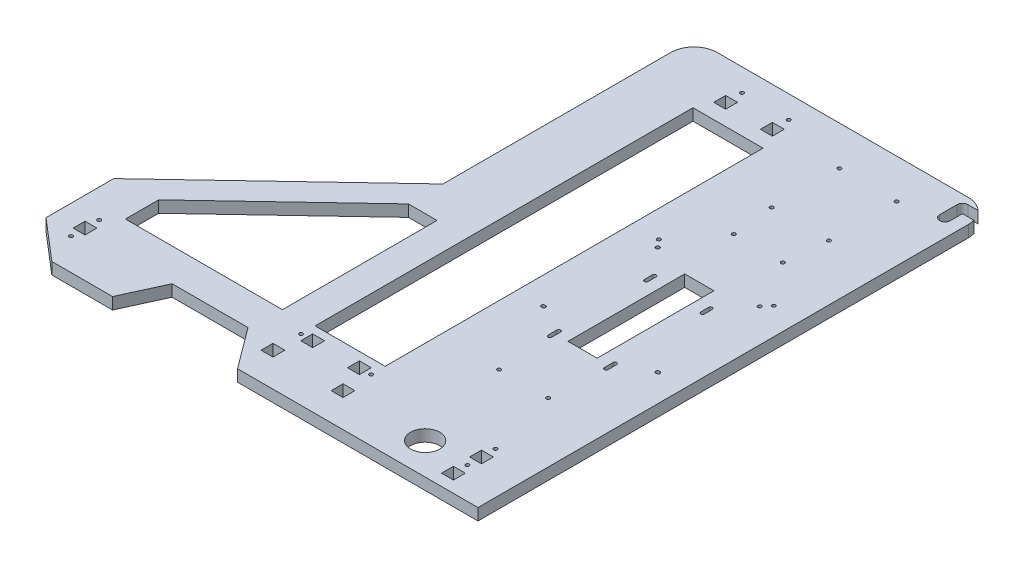
SolidWorks part; units mm, degrees
ref_plane "Front Plane" through (0, 0, 0) normal (0, 0, 1) x (1, 0, 0)
ref_plane "Top Plane" through (0, 0, 0) normal (0, 1, 0) x (1, 0, 0)
ref_plane "Right Plane" through (0, 0, 0) normal (1, 0, 0) x (0, 0, -1)
sketch "Sketch1" plane through (0, 0, 0) normal (0, 1, 0) x (1, 0, 0)
  line L0 (0, 0) -> (-235, 0)
  line L1 (-235, 0) -> (-235, -215)
  line L2 (-235, -215) -> (-380, -352)
  line L3 (-380, -352) -> (-380, -410)
  line L4 (-380, -410) -> (-345, -440)
  line L5 (-345, -440) -> (-293, -440)
  line L6 (-293, -440) -> (-277, -405)
  line L7 (-277, -405) -> (-212, -405)
  line L8 (-212, -405) -> (-185.9255, -440)
  line L9 (-185.9255, -440) -> (0, -440)
  line L10 (0, 0) -> (0, -440)
  line L12 (-293, -440) -> (-185.9255, -440) construction
  dimension "D3" = 235
  dimension "D5" = 58
  dimension "D13" = 190
  dimension "D7" = 35
  dimension "D2" = 126.686
  dimension "D11" = 65
  dimension "D15" = 52
  dimension "D12" = 30
  dimension "D10" = 35
  dimension "D14" = 16
  dimension "D6" = 380
  dimension "D4" = 440
extrude "Boss-Extrude1" add sketch "Sketch1" along normal blind 10
sketch "Sketch16" plane through (0, 10, 0) normal (0, 1, 0) x (1, 0, 0)
  line L0 (0, -440) -> (20, -440)
  line L1 (20, -440) -> (20, 0)
  line L2 (20, 0) -> (0, 0)
  line L3 (0, 0) -> (0, -440)
  dimension "D1" = 20
  dimension "D2" = 90
extrude "Boss-Extrude2" add sketch "Sketch16" against normal through all
sketch "Sketch2" plane through (0, 10, 0) normal (0, 1, 0) x (1, 0, 0)
  line L0 (-235, -215) -> (-235, -405) construction
  line L1 (-277, -405) -> (-212, -405) construction
  line L2 (-345, -440) -> (-345, -318.931) construction
  line L3 (-235, -215) -> (-380, -352) construction
  line L4 (-345, -348.5097) -> (-235, -244.5787)
  line L5 (-235, -244.5787) -> (-210.5, -244.5787)
  line L6 (-210.5, -244.5787) -> (-210.5, -377)
  line L7 (-210.5, -377) -> (-345, -377)
  line L8 (-345, -377) -> (-345, -348.5097)
  line L9 (0, -440) -> (0, 0) construction
  line L10 (-184.5, -375) -> (-124.5, -375)
  line L11 (-184.5, -375) -> (-184.5, -51.35)
  line L12 (-184.5, -51.35) -> (-124.5, -51.35)
  line L13 (-124.5, -375) -> (-124.5, -51.35)
  line L14 (-124.5, -387.1) -> (-184.5, -387.1) construction
  line L15 (-16, -440) -> (-16, 0) construction
  line L16 (20, 0) -> (-235, 0) construction
  line L17 (-355.55, -430.9571) -> (-355.55, -328.899) construction
  line L18 (-21.1, -430.1) -> (-10.9, -430.1)
  line L19 (-21.1, -430.1) -> (-21.1, -419.9)
  line L20 (-21.1, -419.9) -> (-10.9, -419.9)
  line L21 (-10.9, -430.1) -> (-10.9, -419.9)
  line L22 (-21.1, -430.1) -> (-10.9, -419.9) construction
  line L23 (-21.1, -419.9) -> (-10.9, -430.1) construction
  line L24 (-21.1, -406.1) -> (-10.9, -406.1)
  line L25 (-21.1, -406.1) -> (-21.1, -395.9)
  line L26 (-21.1, -395.9) -> (-10.9, -395.9)
  line L27 (-10.9, -406.1) -> (-10.9, -395.9)
  line L28 (-21.1, -406.1) -> (-10.9, -395.9) construction
  line L29 (-21.1, -395.9) -> (-10.9, -406.1) construction
  line L30 (-380, -410) -> (-345, -440) construction
  line L32 (-350.45, -395.9) -> (-360.65, -395.9)
  line L33 (-350.45, -395.9) -> (-350.45, -406.1)
  line L34 (-350.45, -406.1) -> (-360.65, -406.1)
  line L35 (-360.65, -395.9) -> (-360.65, -406.1)
  line L36 (-350.45, -395.9) -> (-360.65, -406.1) construction
  line L37 (-350.45, -406.1) -> (-360.65, -395.9) construction
  line L38 (-185.9255, -440) -> (20, -440) construction
  line L39 (-185.9255, -440) -> (20, -440) construction
  line L40 (-173.924, -33.35) -> (-113.924, -33.35) construction
  line L41 (-154.5, -51.35) -> (-154.5, -33.35) construction
  line L42 (-179.6, -28.25) -> (-169.4, -28.25)
  line L43 (-179.6, -28.25) -> (-179.6, -38.45)
  line L44 (-179.6, -38.45) -> (-169.4, -38.45)
  line L45 (-169.4, -28.25) -> (-169.4, -38.45)
  line L46 (-179.6, -28.25) -> (-169.4, -38.45) construction
  line L47 (-179.6, -38.45) -> (-169.4, -28.25) construction
  line L48 (-129.4, -38.45) -> (-139.6, -28.25) construction
  line L49 (-129.4, -28.25) -> (-139.6, -38.45) construction
  line L50 (-139.6, -28.25) -> (-139.6, -38.45)
  line L51 (-129.4, -38.45) -> (-139.6, -38.45)
  line L52 (-129.4, -28.25) -> (-129.4, -38.45)
  line L53 (-129.4, -28.25) -> (-139.6, -28.25)
  line L54 (-174.5, -33.35) -> (-174.5, -19.35) construction
  line L55 (-134.5, -33.35) -> (-134.5, -19.35) construction
  line L56 (-154.5, -375) -> (-154.5, -440) construction
  line L57 (-174.5, -387.1) -> (-134.5, -387.1) construction
  line L58 (-129.4, -392.2) -> (-139.6, -382) construction
  line L59 (-179.6, -382) -> (-169.4, -382)
  line L60 (-179.6, -382) -> (-179.6, -392.2)
  line L61 (-179.6, -392.2) -> (-169.4, -392.2)
  line L62 (-169.4, -382) -> (-169.4, -392.2)
  line L63 (-179.6, -382) -> (-169.4, -392.2) construction
  line L64 (-179.6, -392.2) -> (-169.4, -382) construction
  line L65 (-129.4, -382) -> (-139.6, -392.2) construction
  line L66 (-139.6, -382) -> (-139.6, -392.2)
  line L67 (-129.4, -392.2) -> (-139.6, -392.2)
  line L68 (-129.4, -382) -> (-129.4, -392.2)
  line L69 (-129.4, -382) -> (-139.6, -382)
  line L70 (-119.4, -416.2) -> (-129.6, -406) construction
  line L71 (-189.6, -406) -> (-179.4, -406)
  line L72 (-189.6, -406) -> (-189.6, -416.2)
  line L73 (-189.6, -416.2) -> (-179.4, -416.2)
  line L74 (-179.4, -406) -> (-179.4, -416.2)
  line L75 (-189.6, -406) -> (-179.4, -416.2) construction
  line L76 (-189.6, -416.2) -> (-179.4, -406) construction
  line L77 (-119.4, -406) -> (-129.6, -416.2) construction
  line L78 (-129.6, -406) -> (-129.6, -416.2)
  line L79 (-119.4, -416.2) -> (-129.6, -416.2)
  line L80 (-119.4, -406) -> (-119.4, -416.2)
  line L81 (-119.4, -406) -> (-129.6, -406)
  line L82 (-360.65, -395.9) -> (-10.9, -395.9) construction
  circle A0 centre (-16, -413) radius 1.55
  circle A1 centre (-16, -389) radius 1.55
  circle A2 centre (-355.55, -413) radius 1.55
  circle A3 centre (-355.55, -389) radius 1.55
  circle A4 centre (-174.5, -19.35) radius 1.55
  circle A5 centre (-134.5, -19.35) radius 1.55
  circle A6 centre (-124.5, -387.1) radius 1.55
  circle A7 centre (-184.5, -387.1) radius 1.55
  point P25 (-16, -425)
  point P30 (-16, -401)
  point P44 (-355.55, -401)
  point P61 (-174.5, -33.35)
  point P72 (-134.5, -33.35)
  point P85 (-174.5, -387.1)
  point P94 (-134.5, -387.1)
  point P95 (-184.5, -411.1)
  point P104 (-124.5, -411.1)
  point P105 (-154.5, -387.1)
  dimension "D13" = 3.1
  dimension "D14" = 3.1
  dimension "D23" = 3.1
  dimension "D24" = 3.1
  dimension "D31" = 3.1
  dimension "D37" = 3.1
  dimension "D1" = 21.5
  dimension "D2" = 28
  dimension "D3" = 24.5
  dimension "D4" = 60
  dimension "D7" = 26
  dimension "D8" = 10.2
  dimension "D9" = 10.2
  dimension "D10" = 10.2
  dimension "D11" = 10.2
  dimension "D12" = 24
  dimension "D15" = 24
  dimension "D19" = 10.2
  dimension "D20" = 10.2
  dimension "D26" = 12
  dimension "D27" = 10.2
  dimension "D28" = 10.2
  dimension "D33" = 10.2
  dimension "D38" = 10.2
  dimension "D39" = 10.2
  dimension "D41" = 24
  dimension "D34" = 30
  dimension "D36" = 12.1
  dimension "D30" = 18
  dimension "D29" = 40
  dimension "D17" = 15
  dimension "D32" = 14
  dimension "D35" = 20
  dimension "D16" = 12
  dimension "D21" = 90
  dimension "D25" = 24
  dimension "D5" = 353.75
  dimension "D22" = 349.75
  dimension "D40" = 30
  dimension "D6" = 65
  dimension "D42" = 0
  dimension "D43" = 0
  dimension "D18" = 16
extrude "Cut-Extrude1" cut sketch "Sketch2" against normal through all
fillet "Fillet1" radius 20 2 edges at (-235, 5, 0) (20, 5, 0)
sketch "Sketch11" plane through (0, 10, 0) normal (0, 1, 0) x (1, 0, 0)
  line L0 (-124.5, -213.175) -> (20, -213.175) construction
  line L1 (20, -440) -> (20, -20) construction
  line L3 (-52.25, -213.175) -> (-52.25, -440) construction
  line L6 (-124.5, -375) -> (-124.5, -51.35) construction
  line L8 (-185.9255, -440) -> (20, -440) construction
  circle A0 centre (-52.25, -413) radius 12.5
  circle A1 centre (-16, -413) radius 1.55 construction
  dimension "D1" = 25
  dimension "D2" = 0
  dimension "D3" = 0
extrude "WiringHole" cut sketch "Sketch11" against normal through all
sketch "Sketch9" [suppressed] plane through (0, 10, 0) normal (0, 1, 0) x (1, 0, 0)
  line L0 (-52.25, -400.5) -> (-52.25, 0) construction
  line L1 (0, 0) -> (-215, 0) construction
  line L2 (-124.5, -213.175) -> (20, -213.175) construction
  line L3 (-124.5, -375) -> (-124.5, -51.35) construction
  line L4 (-4.75, -124.675) -> (-4.75, -301.675) construction
  line L6 (-99.75, -124.675) -> (-4.75, -124.675) construction
  line L7 (-4.75, -301.675) -> (-99.75, -301.675) construction
  line L8 (-99.75, -301.675) -> (-99.75, -124.675) construction
  line L9 (20, -440) -> (20, -20) construction
  circle A0 centre (-52.25, -413) radius 12.5 construction
  circle A1 centre (-99.75, -124.675) radius 1.55
  circle A2 centre (-4.75, -124.675) radius 1.55
  circle A3 centre (-4.75, -301.675) radius 1.55
  circle A4 centre (-99.75, -301.675) radius 1.55
  dimension "D3" = 3.1
  dimension "D4" = 3.1
  dimension "D1" = 95
  dimension "D2" = 177
  dimension "D5" = 47.5
extrude "MountingHoles-PSU" [suppressed] cut sketch "Sketch9" against normal through all
sketch "Sketch10" plane through (0, 10, 0) normal (0, 1, 0) x (1, 0, 0)
  line L0 (-124.5, -213.175) -> (20, -213.175) construction
  line L1 (20, -440) -> (20, -20) construction
  line L2 (-64.75, -228.175) -> (-39.75, -228.175) construction
  line L3 (-52.25, -213.175) -> (-52.25, 0) construction
  line L7 (-124.5, -375) -> (-124.5, -51.35) construction
  line L8 (-64.75, -278.175) -> (-39.75, -278.175)
  line L9 (-64.75, -278.175) -> (-64.75, -178.175)
  line L10 (-64.75, -178.175) -> (-39.75, -178.175)
  line L11 (-39.75, -278.175) -> (-39.75, -178.175)
  line L12 (-64.75, -278.175) -> (-39.75, -178.175) construction
  line L13 (-64.75, -178.175) -> (-39.75, -278.175) construction
  line L15 (0, 0) -> (-215, 0) construction
  line L17 (-52.25, -213.175) -> (-52.25, -440) construction
  line L18 (-185.9255, -440) -> (20, -440) construction
  line L19 (-64.75, -213.175) -> (-39.75, -213.175) construction
  line L20 (-52.25, -278.175) -> (-52.25, -178.175) construction
  dimension "D1" = 25
  dimension "D2" = 100
  dimension "D3" = 0
  dimension "D4" = 0
  dimension "D5" = 0
  dimension "D6" = 15
extrude "WiringSlot" cut sketch "Sketch10" against normal through all
sketch "CenterLines" plane through (0, 10, 0) normal (0, 1, 0) x (1, 0, 0)
  line L0 (-52.25, -278.175) -> (-52.25, -178.175) construction
  line L1 (-64.75, -278.175) -> (-39.75, -278.175) construction
  line L2 (-39.75, -178.175) -> (-64.75, -178.175) construction
  line L3 (-64.75, -228.175) -> (-39.75, -228.175) construction
  line L4 (-64.75, -178.175) -> (-64.75, -278.175) construction
  line L5 (-39.75, -278.175) -> (-39.75, -178.175) construction
ref_plane "Plane1" through (-52.25, 0, 0) normal (1, 0, 0) x (0, 0, -1)
sketch "Sketch6" plane through (0, 10, 0) normal (0, 1, 0) x (1, 0, 0)
  line L0 (-52.25, -278.175) -> (-52.25, -178.175) construction
  line L1 (-76.35, -237.025) -> (-28.15, -237.025) construction
  line L2 (-28.15, -192.575) -> (-28.15, -275.075) construction
  line L3 (-64.75, -278.175) -> (-39.75, -278.175) construction
  line L4 (-64.75, -245.875) -> (-39.75, -245.875) construction
  line L5 (-39.75, -178.175) -> (-64.75, -178.175) construction
  line L6 (-28.15, -192.575) -> (-28.15, -199.575) construction
  line L7 (-26.6, -192.575) -> (-26.6, -199.575)
  line L8 (-29.7, -192.575) -> (-29.7, -199.575)
  line L9 (-64.75, -228.175) -> (-39.75, -228.175) construction
  line L10 (-64.75, -178.175) -> (-64.75, -278.175) construction
  line L11 (-39.75, -278.175) -> (-39.75, -178.175) construction
  line L12 (-28.15, -282.075) -> (-28.15, -275.075) construction
  line L13 (-29.7, -282.075) -> (-29.7, -275.075)
  line L14 (-76.35, -274.475) -> (-76.35, -199.575) construction
  line L15 (-28.15, -282.075) -> (-28.15, -199.575) construction
  line L16 (-26.6, -282.075) -> (-26.6, -275.075)
  arc A2 (-26.6, -192.575) -> (-29.7, -192.575) centre (-28.15, -192.575) ccw
  arc A3 (-29.7, -199.575) -> (-26.6, -199.575) centre (-28.15, -199.575) ccw
  circle A4 centre (-76.35, -274.475) radius 1.55
  circle A6 centre (-76.35, -199.575) radius 1.55
  arc A8 (-29.7, -282.075) -> (-26.6, -282.075) centre (-28.15, -282.075) ccw
  arc A9 (-26.6, -275.075) -> (-29.7, -275.075) centre (-28.15, -275.075) ccw
  point P20 (-28.15, -196.075)
  point P25 (-28.15, -278.575)
  dimension "D8" = 3.1
  dimension "D12" = 3.1
  dimension "D4" = 1.55
  dimension "D5" = 1.55
  dimension "D11" = 82.5
  dimension "D14" = 74.9
  dimension "D2" = 24.1
  dimension "D3" = 48.2
  dimension "D6" = 8.85
  dimension "D9" = 7
  dimension "D10" = 7
extrude "MountingHoles-RAMPS" cut sketch "Sketch6" against normal through all
mirror "Mirror1" about plane through (-52.25, 0, 0) normal (1, 0, 0) of "MountingHoles-RAMPS"
sketch "Sketch5" plane through (0, 10, 0) normal (0, 1, 0) x (1, 0, 0)
  line L0 (-39.75, -228.175) -> (-64.75, -228.175) construction
  line L3 (-39.75, -278.175) -> (-39.75, -178.175) construction
  line L5 (-64.75, -178.175) -> (-64.75, -278.175) construction
  line L7 (-31.25, -127.675) -> (-73.25, -127.675) construction
  line L8 (-31.25, -328.675) -> (-73.25, -328.675) construction
  line L9 (-52.25, -228.175) -> (-52.25, -127.675) construction
  line L10 (-52.25, -228.175) -> (-52.25, -328.675) construction
  circle A0 centre (-73.25, -127.675) radius 1.55
  circle A1 centre (-31.25, -127.675) radius 1.55
  circle A2 centre (-31.25, -328.675) radius 1.55
  circle A3 centre (-73.25, -328.675) radius 1.55
  point P17 (-52.25, -127.675)
  point P22 (-52.25, -328.675)
  dimension "D2" = 3.1
  dimension "D5" = 3.1
  dimension "D6" = 3.1
  dimension "D7" = 3.1
  dimension "D3" = 201
  dimension "D4" = 100.5
  dimension "D8" = 21
  dimension "D9" = 21
  dimension "D10" = 100.5
extrude "MountingHoles-Melzi" cut sketch "Sketch5" against normal through all
sketch "Sketch13" plane through (0, 0, 0) normal (0, -1, 0) x (-1, 0, 0)
  line L0 (64.75, -213.175) -> (124.5, -213.175) construction
  line L1 (124.5, -375) -> (124.5, -51.35) construction
  line L2 (101.46, -262.69) -> (101.46, -163.66) construction
  line L3 (52.25, -278.175) -> (52.25, -178.175) construction
  line L4 (64.75, -178.175) -> (64.75, -278.175) construction
  line L6 (101.46, -262.69) -> (3.56, -262.69) construction
  circle A0 centre (101.46, -163.66) radius 1.55
  circle A1 centre (101.46, -262.69) radius 1.55
  circle A2 centre (8.62, -170.14) radius 1.55
  circle A3 centre (3.56, -262.69) radius 1.55
  point P11 (101.46, -213.175)
  dimension "D8" = 3.1
  dimension "D6" = 3.1
  dimension "D1" = 3.1
  dimension "D2" = 49.515
  dimension "D3" = 49.21
  dimension "D4" = 6.48
  dimension "D5" = 92.84
  dimension "D7" = 97.9
extrude "Mountingholes-Smoothieboard" cut sketch "Sketch13" against normal through all
mirror "Flipped" about plane through (-52.25, 0, 0) normal (1, 0, 0) of "Mountingholes-Smoothieboard"
sketch "Sketch21" plane through (0, 10, 0) normal (0, 1, 0) x (1, 0, 0)
  line L0 (-52.25, -178.175) -> (-52.25, 0) construction
  line L1 (-39.75, -178.175) -> (-64.75, -178.175) construction
  line L2 (0, 0) -> (-215, 0) construction
  line L3 (-52.25, -62.675) -> (-23.3697, -62.675) construction
  circle A0 centre (-27.75, -33.675) radius 1.55
  circle A1 centre (-76.75, -33.675) radius 1.55
  circle A2 centre (-76.75, -91.675) radius 1.55
  circle A3 centre (-27.75, -91.675) radius 1.55
  circle A4 centre (-31.25, -127.675) radius 1.55 construction
  dimension "D1" = 3.1
  dimension "D2" = 24.5
  dimension "D3" = 29
  dimension "D4" = 65
extrude "Pi" cut sketch "Sketch21" against normal through all
sketch "Sketch17" plane through (0, 10, 0) normal (0, 1, 0) x (1, 0, 0)
  line L0 (0, 0) -> (20, 0) construction
  line L1 (20, -23.6361) -> (20, 0) construction
  line L2 (20, -440) -> (20, -20) construction
  line L3 (20, -10) -> (5, -10) construction
  line L4 (20, -14.5) -> (5, -14.5)
  line L5 (20, -5.5) -> (5, -5.5)
  arc A0 (20, -14.5) -> (20, -5.5) centre (20, -10) ccw
  arc A1 (5, -5.5) -> (5, -14.5) centre (5, -10) ccw
  point P8 (12.5, -10)
  dimension "D1" = 9
  dimension "D2" = 15
  dimension "D3" = 10
extrude "Cut-Extrude3" cut sketch "Sketch17" against normal through all
sketch "Sketch18" plane through (0, 10, 0) normal (0, 1, 0) x (1, 0, 0)
  line L0 (5, -5.5) -> (5, -14.5) construction
  line L1 (0.5, -10) -> (5, -10) construction
  line L2 (5, -10) -> (5, -25) construction
  line L3 (9.5, -10) -> (9.5, -25)
  line L4 (0.5, -10) -> (0.5, -25)
  arc A0 (5, -5.5) -> (5, -14.5) centre (5, -10) ccw construction
  arc A1 (9.5, -10) -> (0.5, -10) centre (5, -10) ccw
  arc A2 (0.5, -25) -> (9.5, -25) centre (5, -25) ccw
  point P10 (5, -17.5)
  dimension "D1" = 9
  dimension "D2" = 0
  dimension "D3" = 15
extrude "Cut-Extrude4" cut sketch "Sketch18" against normal through all
sketch "Sketch19" plane through (0, 10, 0) normal (0, 1, 0) x (1, 0, 0)
  line L0 (-5, -25) -> (15, -25) construction
  line L1 (5, -25) -> (5, -5.5) construction
  circle A0 centre (15, -25) radius 1.55
  arc A1 (5, -5.5) -> (0.5, -10) centre (5, -10) ccw construction
  circle A2 centre (-5, -25) radius 1.55
  dimension "D2" = 3.1
extrude "Cut-Extrude5" [suppressed] cut sketch "Sketch19" against normal through all
equation "\"Y-ROD-SPACING\"=75"
equation "\"Y-BED-OFFSET\"=2"
equation "\"Y-BED-ROD-INSET\"=3.5"
equation "\"T-SLOT-NUT-FILLET-RADIUS\"=0.25"
equation "\"T-SLOT-SCREW-SHAFT-RADIUS\"=1.75"
equation "\"T-SLOT-SCREW-SHAFT-CUTOUT-LENGTH\"=10.5"
equation "\"T-SLOT-NUT-DEPTH\"=4.2"
equation "\"T-SLOT-NUT-WIDTH\"=3"
equation "\"T-SLOT-NUT-END-DISTANCE\"=8"
equation "\"ACRYLIC-TAB-CUTOUT-SIZE\"=\"ACRYLIC-THICKNESS\"+\"ACRYLIC-TAB-TOLERANCE\"*2"
equation "\"ACRYLIC-TAB-WIDTH\"=\"ACRYLIC-THICKNESS\""
equation "\"ACRYLIC-M3-HOLE\"=3.1"
equation "\"SMOOTHROD-CAP-SCREW-DISTANCE\"=20"
equation "\"FRAME-WIDTH-INNER\"=370"
equation "\"D24@Sketch2\"=\"ACRYLIC-M3-HOLE\""
equation "\"D23@Sketch2\"=\"ACRYLIC-M3-HOLE\""
equation "\"D19@Sketch2\"=\"ACRYLIC-THICKNESS\"+\"ACRYLIC-TAB-TOLERANCE\"*2"
equation "\"D20@Sketch2\"=\"ACRYLIC-TAB-WIDTH\"+\"ACRYLIC-TAB-TOLERANCE\"*2"
equation "\"D37@Sketch2\"=\"ACRYLIC-M3-HOLE\""
equation "\"D33@Sketch2\"=\"ACRYLIC-TAB-CUTOUT-SIZE\""
equation "\"D38@Sketch2\"=\"ACRYLIC-TAB-CUTOUT-SIZE\""
equation "\"D39@Sketch2\"=\"ACRYLIC-TAB-CUTOUT-SIZE\""
equation "\"D13@Sketch2\"=\"ACRYLIC-M3-HOLE\""
equation "\"D14@Sketch2\"=\"ACRYLIC-M3-HOLE\""
equation "\"D8@Sketch2\"=\"ACRYLIC-TAB-CUTOUT-SIZE\""
equation "\"D9@Sketch2\"=\"ACRYLIC-TAB-CUTOUT-SIZE\""
equation "\"D10@Sketch2\"=\"ACRYLIC-TAB-CUTOUT-SIZE\""
equation "\"D11@Sketch2\"=\"ACRYLIC-TAB-CUTOUT-SIZE\""
equation "\"D31@Sketch2\"=\"ACRYLIC-M3-HOLE\""
equation "\"D27@Sketch2\"=\"ACRYLIC-THICKNESS\"+\"ACRYLIC-TAB-TOLERANCE\"*2"
equation "\"D28@Sketch2\"=\"ACRYLIC-TAB-WIDTH\"+\"ACRYLIC-TAB-TOLERANCE\"*2"
equation "\"NEMA17-HOLE-SPACING\"=31"
equation "\"NEMA17-CENTRAL-CUTOUT\"=22.5"
equation "\"Z-BRACKET-REACH\"=55"
equation "\"TOP-BRACKET-SPACING\"=40"
equation "\"D29@Sketch2\"=\"TOP-BRACKET-SPACING\""
equation "\"ACRYLIC-THICKNESS\"=10"
equation "\"SMOOTHROD-Z-LENGTH\"=350"
equation "\"D5@Sketch2\"=\"SMOOTHROD-Z-LENGTH\"-\"SMOOTHROD-TIGHTENING-HEADROOM\"+4"
equation "\"SMOOTHROD-X-LENGTH\"=350"
equation "\"SMOOTHROD-Y-LENGTH\"=350"
equation "\"D22@Sketch2\"=\"SMOOTHROD-Y-LENGTH\"-\"SMOOTHROD-TIGHTENING-HEADROOM\""
equation "\"SMOOTHROD-TIGHTENING-HEADROOM\"=.25"
equation "\"X-ROD-SPACING\"=45"
equation "\"Z-ROD-SPACING\"=17.5"
equation "\"LEADSCREW-Z-LENGTH\"=300"
equation "\"SCREW-HEAD-RADIUS\"=6"
equation "\"PRINTED-X-SMOOTHROD-DIAMETER\"=8.2"
equation "\"PRINTED-X-SMOOTHROD-CUTOUT\"=10"
equation "\"PRINTED-X-BASE-HEIGHT\"=10"
equation "\"PRINTED-LM8UU-CUTOUT-SIZE\"=15.25"
equation "\"PRINTED-LM8UU-CUTOUT-LENGTH\"=24.5"
equation "\"PRINTED-X-IDLER-HEIGHT\"=16"
equation "\"PSU-MOUNTING-WIDTH\"=95"
equation "\"PSU-MOUNTING-HEIGHT\"=177"
equation "\"D1@Sketch9\"=\"PSU-MOUNTING-WIDTH\""
equation "\"D3@Sketch9\"=\"ACRYLIC-M3-HOLE\""
equation "\"D1@Boss-Extrude1\"=\"ACRYLIC-THICKNESS\""
equation "\"D6@Sketch1\"=\"SMOOTHROD-Y-LENGTH\"+30"
equation "\"D4@Sketch9\"=\"ACRYLIC-M3-HOLE\""
equation "\"D2@Sketch9\"=\"PSU-MOUNTING-HEIGHT\""
equation "\"D5@Sketch9\"=\"PSU-MOUNTING-WIDTH\"/2"
equation "\"D4@Sketch1\"=\"SMOOTHROD-Z-LENGTH\"+90"
equation "\"D8@Sketch6\"=\"ACRYLIC-M3-HOLE\""
equation "\"D12@Sketch6\"=\"ACRYLIC-M3-HOLE\""
equation "\"D2@Sketch5\"=\"ACRYLIC-M3-HOLE\""
equation "\"D5@Sketch5\"=\"ACRYLIC-M3-HOLE\""
equation "\"D6@Sketch5\"=\"ACRYLIC-M3-HOLE\""
equation "\"D7@Sketch5\"=\"ACRYLIC-M3-HOLE\""
equation "\"D1@Sketch13\"=\"ACRYLIC-M3-HOLE\""
equation "\"D6@Sketch13\"=\"ACRYLIC-M3-HOLE\""
equation "\"D8@Sketch13\"=\"ACRYLIC-M3-HOLE\""
equation "\"D4@Sketch6\"=\"ACRYLIC-M3-HOLE\"/2"
equation "\"D5@Sketch6\"=\"ACRYLIC-M3-HOLE\"/2"
equation "\"Y-BED-SCREW-SPACING\"=209"
equation "\"Y-BED-SCREW-CUTOUT-SLOT-HEIGHT\"=2"
equation "\"ACRYLIC-THICKNESS2\"=4.5"
equation "\"ACRYLIC-TAB-TOLERANCE\"=.1"
equation "\"Z-ROD-INSET\"=16"
equation "\"SCREW-LENGTH-FRAME\"=\"ACRYLIC-THICKNESS\" + 10"
equation "\"SCREW-LENGTH-MOTOR\"=\"ACRYLIC-THICKNESS\" + 5"
equation "\"SCREW-LENGTH-EXTRUDER\"=28"
equation "\"Y-BELT-TO-ROD-DISTANCE\"=20"
equation "\"SPOOL-HOLDER-ROD-SPACING\"=150"
equation "\"ACRYLIC-X-CARRIAGE-WIDTH\"=55"
equation "\"ACRYLIC-X-CARRIAGE-HEIGHT\"=75"
equation "\"ACRYLIC-X-CARRIAGE-LM8UU-CUTOUT-WIDTH\"=24.25"
equation "\"ACRYLIC-X-CARRIAGE-SCREW-SPACING-X\"=15"
equation "\"ACRYLIC-X-CARRIAGE-SCREW-SPACING-Y\"=33"
equation "\"ACRYLIC-X-CARRIAGE-CENTER-TAB-SPACING\"=14"
equation "\"ACRYLIC-X-CARRIAGE-EXTRUDER-OFFSET\"=26"
equation "\"ACRYLIC-X-CARRIAGE-EXTRUDER-ANGLE\"=90"
equation "\"ACRYLIC-X-CARRIAGE-EXTRUDER-SHELF-DEPTH\"=\"ACRYLIC-X-CARRIAGE-EXTRUDER-OFFSET\" + 28"
equation "\"ACRYLIC-X-CARRIAGE-EXTRUDER-BRACE-SPACING\"=23"
equation "\"ACRYLIC-X-CARRIAGE-EXTRUDER-BRACE-TAB-OFFSET\"=20"
equation "\"ACRYLIC-X-CARRIAGE-EXTRUDER-BRACE-HEIGHT\"=35"
equation "\"ACRYLIC-X-CARRIAGE-EXTRUDER-BRACE-SCREW-SPACING\"=22"
equation "\"D1@Sketch19\"=\"SMOOTHROD-CAP-SCREW-DISTANCE\"/2"
equation "\"D2@Sketch19\"=\"ACRYLIC-M3-HOLE\""
equation "\"D1@Sketch21\"=\"ACRYLIC-M3-HOLE\""
